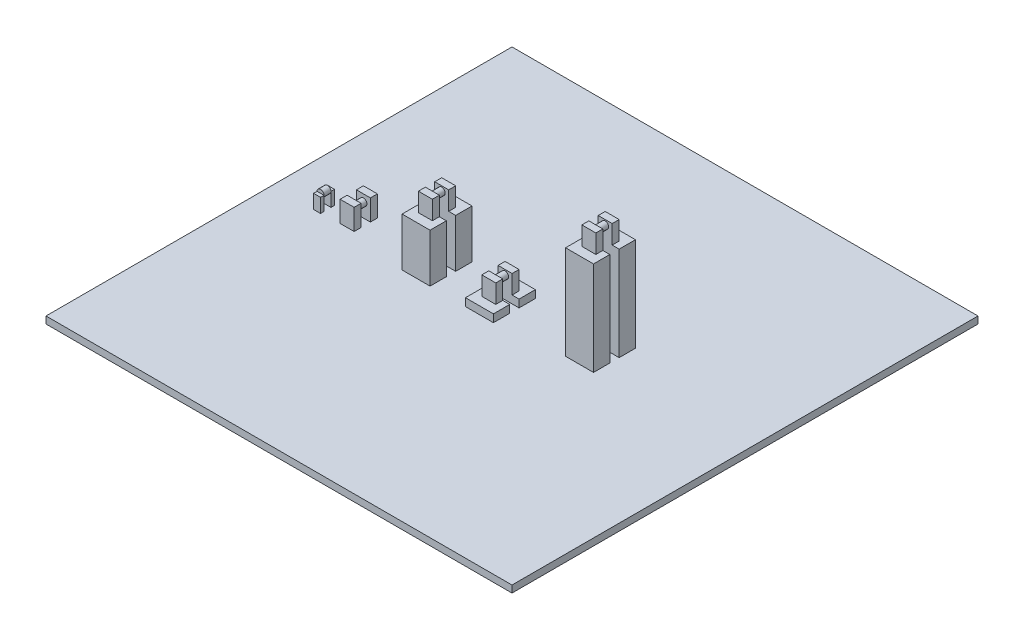
SolidWorks part; units mm, degrees
ref_plane "前基準面" through (0, 0, 0) normal (0, 0, 1) x (1, 0, 0)
ref_plane "上基準面" through (0, 0, 0) normal (0, 1, 0) x (1, 0, 0)
ref_plane "右基準面" through (0, 0, 0) normal (1, 0, 0) x (0, 0, -1)
sketch "草圖1" plane through (0, 0, 0) normal (0, 1, 0) x (1, 0, 0)
  line L1 (-50, 50) -> (50, 50)
  line L2 (-50, 50) -> (-50, -50)
  line L3 (-50, -50) -> (50, -50)
  line L4 (50, 50) -> (50, -50)
  line L5 (-50, 50) -> (50, -50) construction
  line L6 (-50, -50) -> (50, 50) construction
  point P0 (0, 0)
  dimension "D1" = 100
  dimension "D2" = 100
extrude "填料-伸長1" add sketch "草圖1" along normal blind 1.5
sketch "草圖2" plane through (0, 0, 0) normal (0, 0, 1) x (1, 0, 0)
  line L0 (-50, 1.5) -> (50, 1.5) construction
  circle A0 centre (-40.3368, 4.5) radius 0.75
  point P2 (-40.3368, 3.498)
  dimension "D1" = 1.5
  dimension "D2" = 3
extrude "填料-伸長2" add sketch "草圖2" along normal mid plane 1.5 separate body
sketch "草圖3" plane through (0, 0, 0.75) normal (0, 0, 1) x (1, 0, 0)
  line L0 (-50, 1.5) -> (50, 1.5) construction
  line L1 (-41.0868, 4.5) -> (-39.5868, 4.5)
  line L2 (-41.0868, 4.5) -> (-41.0868, 1.5)
  line L3 (-41.0868, 1.5) -> (-39.5868, 1.5)
  line L4 (-39.5868, 4.5) -> (-39.5868, 1.5)
  circle A0 centre (-40.3368, 4.5) radius 0.75 construction
  dimension "D2" = 0.75
  dimension "D1" = 1.5
  dimension "D3" = 3
extrude "填料-伸長3" add sketch "草圖3" along normal blind 1.5
mirror "鏡射1" about plane through (0, 0, 0) normal (0, 0, 1) of "填料-伸長3"
sketch "草圖5" plane through (0, 4.5, 0) normal (0, 1, 0) x (1, 0, 0)
  line L1 (-35.6368, 0.25) -> (-32.6368, 0.25)
  line L2 (-35.6368, 0.25) -> (-35.6368, -1.25)
  line L3 (-35.6368, -1.25) -> (-32.6368, -1.25)
  line L4 (-32.6368, 0.25) -> (-32.6368, -1.25)
  line L9 (-35.6368, 2.25) -> (-32.6368, 2.25)
  line L10 (-35.6368, 2.25) -> (-35.6368, 3.75)
  line L11 (-35.6368, 3.75) -> (-32.6368, 3.75)
  line L12 (-32.6368, 2.25) -> (-32.6368, 3.75)
  dimension "D3" = 1.5
  dimension "D4" = 3
  dimension "D5" = 1.5
  dimension "D6" = 3
  dimension "D7" = 2
extrude "填料-伸長4" add sketch "草圖5" against normal up to surface (3 mm away) up to face at (-40.3368, 1.5, -1.5)
sketch "草圖7" plane through (0, 0, -2.25) normal (0, 0, 1) x (1, 0, 0)
  line L0 (-35.6368, 1.5) -> (-35.6368, 4.5) construction
  line L1 (-32.6368, 1.5) -> (-35.6368, 1.5) construction
  circle A0 centre (-34.1368, 4.5) radius 0.75
  dimension "D1" = 1.5
  dimension "D2" = 1.5
  dimension "D3" = 3
extrude "填料-伸長5" add sketch "草圖7" along normal blind 2.5
sketch "草圖8" plane through (0, 1.5, 0) normal (0, 1, 0) x (1, 0, 0)
  line L0 (-32.6368, 3.75) -> (-35.6368, 3.75) construction
  line L1 (-20.3368, 5.75) -> (-14.3368, 5.75)
  line L2 (-20.3368, 5.75) -> (-20.3368, -3.25)
  line L3 (-20.3368, -3.25) -> (-14.3368, -3.25)
  line L4 (-14.3368, 5.75) -> (-14.3368, -3.25)
  line L5 (-20.3368, 5.75) -> (-14.3368, -3.25) construction
  line L6 (-20.3368, -3.25) -> (-14.3368, 5.75) construction
  line L7 (-35.6368, 2.25) -> (-34.8868, 2.25) construction
  line L8 (-35.6368, 3.75) -> (-32.6368, 3.75) construction
  point P0 (-17.3368, 1.25)
  point P7 (-34.1368, 3.75)
  point P8 (-17.3368, 1.71)
  dimension "D1" = 16.8
  dimension "D2" = 6
  dimension "D3" = 1
  dimension "D4" = 2
extrude "填料-伸長6" add sketch "草圖8" along normal blind 10.4
sketch "草圖9" plane through (0, 11.9, 0) normal (0, 1, 0) x (1, 0, 0)
  line L0 (-32.6368, 3.75) -> (-35.6368, 3.75) construction
  line L1 (-18.8368, 3.75) -> (-15.8368, 3.75)
  line L2 (-18.8368, 3.75) -> (-18.8368, 2.25)
  line L3 (-18.8368, 2.25) -> (-15.8368, 2.25)
  line L4 (-15.8368, 3.75) -> (-15.8368, 2.25)
  line L5 (-35.6368, 2.25) -> (-35.6368, 3.75) construction
  line L6 (-22.4008, 1.25) -> (-12.2755, 1.25) construction
  line L7 (-15.8368, -1.25) -> (-15.8368, 0.25)
  line L8 (-18.8368, 0.25) -> (-15.8368, 0.25)
  line L9 (-18.8368, -1.25) -> (-18.8368, 0.25)
  line L10 (-18.8368, -1.25) -> (-15.8368, -1.25)
  point P8 (-35.6368, 3)
  point P11 (-22.4008, 1.25)
  dimension "D1" = 1.5
  dimension "D2" = 3
  dimension "D3" = 16.8
  dimension "D4" = 1
extrude "填料-伸長7" add sketch "草圖9" along normal blind 4
sketch "草圖10" plane through (0, 0, -2.25) normal (0, 0, 1) x (1, 0, 0)
  line L0 (-20.3368, 11.9) -> (-14.3368, 11.9) construction
  line L1 (-18.8368, 15.9) -> (-18.8368, 11.9) construction
  circle A0 centre (-17.3368, 14.9) radius 0.75
  point P4 (0, 0)
  dimension "D1" = 1.5
  dimension "D2" = 3
  dimension "D3" = 1.5
extrude "填料-伸長8" add sketch "草圖10" along normal blind 3
sketch "草圖11" plane through (0, 11.9, 0) normal (0, 1, 0) x (1, 0, 0)
  line L0 (-20.3368, 5.75) -> (-20.3368, -3.25) construction
  line L1 (-20.3368, 2.25) -> (-14.3368, 2.25)
  line L2 (-20.3368, 2.25) -> (-20.3368, 0.25)
  line L3 (-20.3368, 0.25) -> (-14.3368, 0.25)
  line L4 (-14.3368, 2.25) -> (-14.3368, 0.25)
  line L5 (-14.3368, -3.25) -> (-14.3368, 5.75) construction
  line L6 (-15.8368, 0.25) -> (-18.8368, 0.25) construction
  line L7 (-18.8368, 2.25) -> (-15.8368, 2.25) construction
extrude "除料-伸長1" cut sketch "草圖11" against normal up to surface (10.4 mm away) up to face at (-34.1368, 1.5, -3)
sketch "草圖12" plane through (0, 1.5, 0) normal (0, 1, 0) x (1, 0, 0)
  line L1 (13.2432, 1.75) -> (19.2432, 1.75)
  line L2 (13.2432, 1.75) -> (13.2432, -1.75)
  line L3 (13.2432, -1.75) -> (19.2432, -1.75)
  line L4 (19.2432, 1.75) -> (19.2432, -1.75)
  line L5 (-14.3368, 0.25) -> (-20.3368, 0.25) construction
  line L7 (-20.3368, 0.25) -> (-20.3368, -3.25) construction
  line L8 (11.5568, 2.75) -> (25.799, 2.75) construction
  line L9 (19.2432, 3.75) -> (19.2432, 7.25)
  line L10 (13.2432, 7.25) -> (19.2432, 7.25)
  line L11 (13.2432, 3.75) -> (13.2432, 7.25)
  line L12 (13.2432, 3.75) -> (19.2432, 3.75)
  dimension "D1" = 3.5
  dimension "D2" = 1.5
  dimension "D3" = 6
  dimension "D4" = 33.58
  dimension "D5" = 1
extrude "填料-伸長9" add sketch "草圖12" along normal blind 20.17
sketch "草圖13" plane through (0, 21.67, 0) normal (0, 1, 0) x (1, 0, 0)
  line L0 (19.2432, 1.75) -> (13.2432, 1.75) construction
  line L1 (14.7432, 1.75) -> (17.7432, 1.75)
  line L2 (14.7432, 1.75) -> (14.7432, 0.25)
  line L3 (14.7432, 0.25) -> (17.7432, 0.25)
  line L4 (17.7432, 1.75) -> (17.7432, 0.25)
  line L8 (19.2432, -1.75) -> (19.2432, 1.75) construction
  line L9 (13.2432, 1.75) -> (13.2432, -1.75) construction
  line L10 (11.5568, 2.75) -> (25.799, 2.75) construction
  line L11 (11.5568, 2.75) -> (25.799, 2.75) construction
  line L12 (17.7432, 3.75) -> (17.7432, 5.25)
  line L13 (14.7432, 5.25) -> (17.7432, 5.25)
  line L14 (14.7432, 3.75) -> (14.7432, 5.25)
  line L15 (14.7432, 3.75) -> (17.7432, 3.75)
  dimension "D1" = 1.5
  dimension "D2" = 1.5
  dimension "D3" = 1.5
extrude "填料-伸長10" add sketch "草圖13" along normal blind 4
sketch "草圖14" plane through (0, 0, -3.75) normal (0, 0, 1) x (1, 0, 0)
  line L0 (14.7432, 25.67) -> (14.7432, 21.67) construction
  line L1 (13.2432, 21.67) -> (19.2432, 21.67) construction
  circle A0 centre (16.2432, 24.67) radius 0.75
  dimension "D1" = 1.5
  dimension "D2" = 1.5
  dimension "D3" = 3
extrude "填料-伸長11" add sketch "草圖14" along normal up to surface (2 mm away) up to face at (16.2432, 17.6275, -1.75)
pattern_linear "直線複製排列2" count 2 spacing 13.6 along (1, 0, 0) of "填料-伸長6"
sketch "草圖16" plane through (0, 0, 0) normal (0, 0, 1) x (1, 0, 0)
  line L0 (-6.7368, 11.9) -> (-6.7368, 1.5) construction
  line L1 (-6.7368, 3.15) -> (-0.7368, 3.15)
  line L2 (-6.7368, 3.15) -> (-6.7368, 11.9)
  line L3 (-6.7368, 11.9) -> (-0.7368, 11.9)
  line L4 (-0.7368, 3.15) -> (-0.7368, 11.9)
  line L5 (-6.7368, 1.5) -> (-0.7368, 1.5) construction
  dimension "D1" = 1.65
extrude "除料-伸長2" cut sketch "草圖16" against normal mid plane 18.5
sketch "草圖17" plane through (0, 3.15, 0) normal (0, 1, 0) x (1, 0, 0)
  line L0 (-6.7368, 2.25) -> (-0.7368, 2.25)
  line L1 (-6.7368, 0.25) -> (-0.7368, 0.25)
  line L2 (-0.7368, -3.25) -> (-0.7368, 5.75) construction
  line L3 (-6.7368, 5.75) -> (-6.7368, -3.25) construction
  line L4 (-0.7368, 0.25) -> (-0.7368, 2.25)
  line L5 (-6.7368, 2.25) -> (-6.7368, 0.25)
  line L6 (-6.7368, 5.75) -> (-0.7368, 5.75) construction
  dimension "D1" = 2
  dimension "D2" = 3.5
extrude "除料-伸長3" cut sketch "草圖17" against normal up to surface (1.65 mm away) up to face at (-17.3368, 1.5, 1.5)
sketch "草圖18" plane through (0, 3.15, 0) normal (0, 1, 0) x (1, 0, 0)
  line L0 (-6.7368, 2.25) -> (-0.7368, 2.25) construction
  line L1 (-5.2368, 2.25) -> (-2.2368, 2.25)
  line L2 (-5.2368, 2.25) -> (-5.2368, 3.75)
  line L3 (-5.2368, 3.75) -> (-2.2368, 3.75)
  line L4 (-2.2368, 2.25) -> (-2.2368, 3.75)
  line L5 (-0.7368, 5.75) -> (-0.7368, 2.25) construction
  line L7 (-6.7368, 0.25) -> (-0.7368, 0.25) construction
  line L8 (-5.2368, 0.25) -> (-2.2368, 0.25)
  line L9 (-5.2368, 0.25) -> (-5.2368, -1.25)
  line L10 (-5.2368, -1.25) -> (-2.2368, -1.25)
  line L11 (-2.2368, 0.25) -> (-2.2368, -1.25)
  dimension "D1" = 3
  dimension "D2" = 1.5
  dimension "D3" = 1.5
  dimension "D4" = 1.5
extrude "填料-伸長12" add sketch "草圖18" along normal blind 4
sketch "草圖19" plane through (0, 0, -2.25) normal (0, 0, 1) x (1, 0, 0)
  line L0 (-5.2368, 3.15) -> (-2.2368, 3.15) construction
  line L1 (-5.2368, 7.15) -> (-5.2368, 3.15) construction
  circle A0 centre (-3.7368, 6.15) radius 0.75
  dimension "D1" = 1.5
  dimension "D2" = 3
  dimension "D3" = 1.5
extrude "填料-伸長13" add sketch "草圖19" along normal blind 3
sketch "草圖20" plane through (0, 4.5, 0) normal (0, 1, 0) x (1, 0, 0)
  line L0 (-32.6368, 0.25) -> (-33.3868, 0.25) construction
  line L1 (-33.3868, 0.25) -> (-33.3868, -0.25) construction
  line L2 (-33.3868, -0.25) -> (-34.8868, -0.25) construction
  line L3 (-34.8868, -0.25) -> (-34.8868, 0.25) construction
  line L4 (-34.8868, 0.25) -> (-35.6368, 0.25) construction
  line L5 (-35.6368, 0.25) -> (-35.6368, -1.25) construction
  line L6 (-35.6368, -1.25) -> (-32.6368, -1.25) construction
  line L7 (-32.6368, -1.25) -> (-32.6368, 0.25) construction
  line L8 (-35.6368, 3.75) -> (-35.6368, 2.25) construction
  line L9 (-35.6368, 2.25) -> (-34.8868, 2.25) construction
  line L10 (-34.8868, 2.25) -> (-33.3868, 2.25) construction
  line L11 (-33.3868, 2.25) -> (-32.6368, 2.25) construction
  line L12 (-32.6368, 2.25) -> (-32.6368, 3.75) construction
  line L13 (-32.6368, 3.75) -> (-35.6368, 3.75) construction
  line L14 (-32.6368, 0.25) -> (-33.3868, 0.25)
  line L15 (-33.3868, 0.25) -> (-33.3868, -0.25)
  line L16 (-33.3868, -0.25) -> (-34.8868, -0.25)
  line L17 (-34.8868, -0.25) -> (-34.8868, 0.25)
  line L18 (-34.8868, 0.25) -> (-35.6368, 0.25)
  line L19 (-35.6368, 0.25) -> (-35.6368, -1.25)
  line L20 (-35.6368, -1.25) -> (-32.6368, -1.25)
  line L21 (-32.6368, -1.25) -> (-32.6368, 0.25)
  line L22 (-35.6368, 3.75) -> (-35.6368, 2.25)
  line L23 (-35.6368, 2.25) -> (-34.8868, 2.25)
  line L24 (-34.8868, 2.25) -> (-33.3868, 2.25)
  line L25 (-33.3868, 2.25) -> (-32.6368, 2.25)
  line L26 (-32.6368, 2.25) -> (-32.6368, 3.75)
  line L27 (-32.6368, 3.75) -> (-35.6368, 3.75)
extrude "填料-伸長14" add sketch "草圖20" along normal blind 1.5
sketch "草圖21" plane through (-41.0868, 0, 0) normal (-1, 0, 0) x (0, 0, 1)
  line L0 (2.25, 1.5) -> (0.75, 1.5) construction
  line L1 (1.5, 1.5) -> (2.25, 1.5)
  line L2 (1.5, 1.5) -> (1.5, 4.5)
  line L3 (1.5, 4.5) -> (2.25, 4.5)
  line L4 (2.25, 1.5) -> (2.25, 4.5)
  line L5 (-2.25, 1.5) -> (-0.75, 1.5) construction
  line L6 (-1.5, 1.5) -> (-2.25, 1.5)
  line L7 (-1.5, 1.5) -> (-1.5, 4.5)
  line L8 (-1.5, 4.5) -> (-2.25, 4.5)
  line L9 (-2.25, 1.5) -> (-2.25, 4.5)
extrude "除料-伸長4" cut sketch "草圖21" against normal blind 1.5
sketch "草圖22" plane through (0, 6, 0) normal (0, 1, 0) x (1, 0, 0)
  line L1 (-34.8868, 0.25) -> (-33.3868, 0.25)
  line L2 (-34.8868, 0.25) -> (-34.8868, -0.25)
  line L3 (-34.8868, -0.25) -> (-33.3868, -0.25)
  line L4 (-33.3868, 0.25) -> (-33.3868, -0.25)
extrude "填料-伸長15" add sketch "草圖22" against normal blind 2.5
